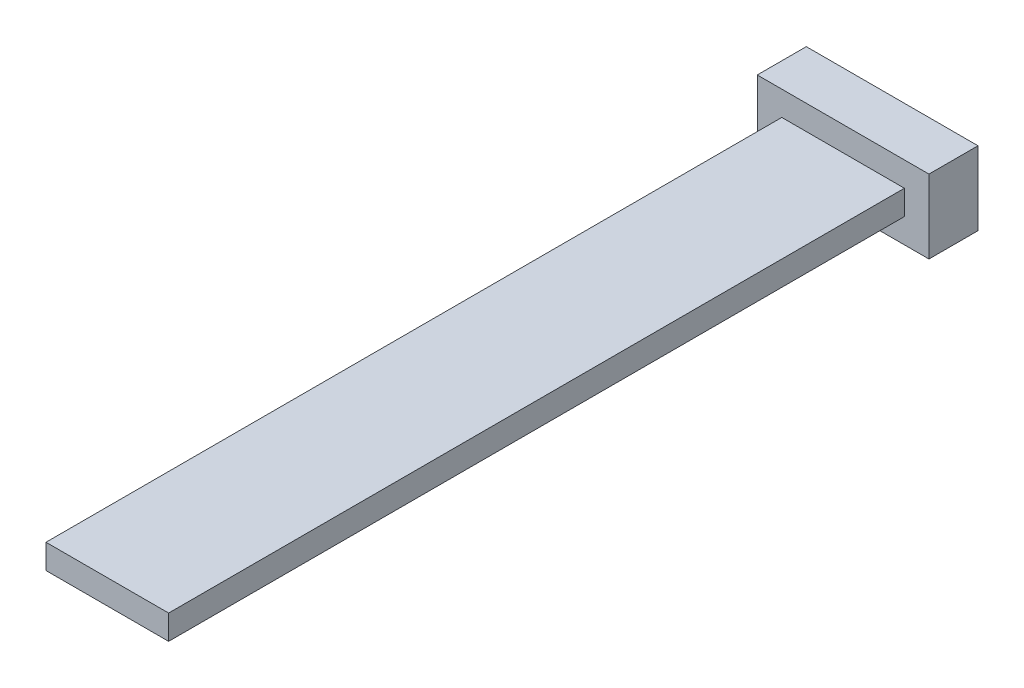
SolidWorks part; units mm, degrees
ref_plane "Front Plane" through (0, 0, 0) normal (0, 0, 1) x (1, 0, 0)
ref_plane "Top Plane" through (0, 0, 0) normal (0, 1, 0) x (1, 0, 0)
ref_plane "Right Plane" through (0, 0, 0) normal (1, 0, 0) x (0, 0, -1)
sketch "Sketch1" plane through (0, 0, 0) normal (0, 0, 1) x (1, 0, 0)
  line L1 (0, 0) -> (50, 0)
  line L2 (0, 0) -> (0, 10)
  line L3 (0, 10) -> (50, 10)
  line L4 (50, 0) -> (50, 10)
  dimension "D1" = 50
  dimension "D2" = 10
extrude "Boss-Extrude1" add sketch "Sketch1" along normal blind 300
sketch "Sketch2" plane through (0, 0, 0) normal (0, 0, -1) x (-1, 0, 0)
  line L0 (-50, 0) -> (-50, 10) construction
  line L1 (10, 20) -> (-60, 20)
  line L2 (10, 20) -> (10, -10)
  line L3 (10, -10) -> (-60, -10)
  line L4 (-60, 20) -> (-60, -10)
  line L6 (-50, 10) -> (0, 10) construction
  dimension "D1" = 70
  dimension "D2" = 10
  dimension "D3" = 30
  dimension "D4" = 10
extrude "Boss-Extrude2" add sketch "Sketch2" along normal blind 20
ref_point "Point1"
ref_point "Point2"
ref_axis "Axis1" through (25, 5, 300) along (0, 0, -1)
